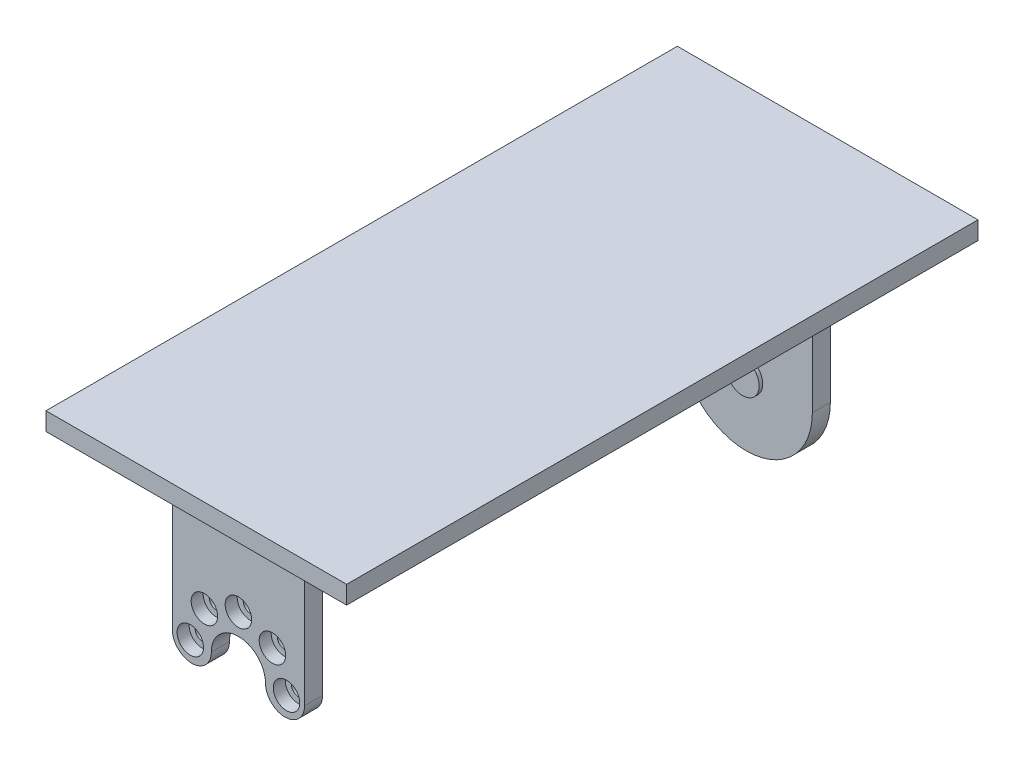
SolidWorks part; units mm, degrees
ref_plane "Plano frontal" through (0, 0, 0) normal (0, 0, 1) x (1, 0, 0)
ref_plane "Plano superior" through (0, 0, 0) normal (0, 1, 0) x (1, 0, 0)
ref_plane "Plano direito" through (0, 0, 0) normal (1, 0, 0) x (0, 0, -1)
sketch "Esboço1" plane through (0, 0, 0) normal (0, 0, 1) x (1, 0, 0)
  line L0 (11, 0) -> (11, 25)
  line L1 (11, 25) -> (-11, 25)
  line L2 (-11, 25) -> (-11, 0)
  arc A3 (11, 0) -> (4.5, 0) centre (7.75, 0) cw
  arc A8 (4.5, 0) -> (-4.5, 0) centre (0, 0) ccw
  arc A10 (-4.5, 0) -> (-11, 0) centre (-7.75, 0) cw
  dimension "D1" = 25
extrude "Ressalto-extrusão1" add sketch "Esboço1" along normal blind 3
sketch "Esboço2" plane through (0, 25, 0) normal (0, 1, 0) x (1, 0, 0)
  line L1 (-25, -10) -> (25, -10)
  line L2 (-25, -10) -> (-25, 95)
  line L3 (-25, 95) -> (25, 95)
  line L4 (25, -10) -> (25, 95)
  line L5 (11, -3) -> (-11, -3) construction
  point P7 (0, -3)
  point P8 (0, -10)
  dimension "D1" = 105
  dimension "D2" = 50
  dimension "D3" = 7
extrude "Ressalto-extrusão2" add sketch "Esboço2" along normal blind 3
ref_plane "Plano1" through (0, 0, -81.45) normal (0, 0, -1) x (-1, 0, 0)
sketch "Esboço3" plane through (0, 0, -81.45) normal (0, 0, -1) x (-1, 0, 0)
  line L1 (-11, 0) -> (-11, 25)
  line L2 (-11, 25) -> (11, 25)
  line L3 (11, 25) -> (11, 0)
  arc A0 (-11, 0) -> (11, 0) centre (0, 0) ccw
  dimension "D1" = 22
extrude "Ressalto-extrusão3" add sketch "Esboço3" along normal blind 3
hole_wizard "Rebaixo para SHCS M21" positions "Esboço4" profile "Esboço5" counterbore size "M2" standard "Ansi Metric" end condition up to next
sketch "Esboço4" plane through (0, 0, 3) normal (0, 0, 1) x (1, 0, 0)
  arc A0 (8.8, 0) -> (7.2, 0) centre (8, 0) ccw construction
  point P0 (8, 0)
sketch "Esboço5" plane through (8, 0, 3) normal (1, 0, 0) x (0, -1, 0)
  line L0 (0, 0) -> (0, 3)
  line L1 (0, 3) -> (1.2, 3)
  line L3 (1.2, 3) -> (1.2, 2)
  line L4 (1.2, 2) -> (2.2, 2)
  line L5 (2.2, 2) -> (2.2, 0)
  line L7 (2.2, 0) -> (0, 0)
  line L11 (0, -6.35) -> (0, 107.95) construction
  dimension "Thru Hole Dia." = 2.4
  dimension "Thru Hole Depth" = 3
  dimension "C'Bore Dia." = 4.4
  dimension "C'Bore Depth" = 2
pattern_circular "PadrãoCircular1" count 5 over 180 about axis through (0, 0, 3) along (0, 0, -1) of "Rebaixo para SHCS M21" reverse direction yes
sketch "Esboço6" plane through (0, 0, 0) normal (1, 0, 0) x (0, 0, -1)
  line L0 (-10, 25) -> (-3, 25) construction
  line L3 (-3, 25) -> (-3, 18) construction
  line L4 (-3, 0) -> (-3, 25) construction
  line L5 (-3, 18) -> (-10, 25)
rib "Nervura1" sketch "Esboço6" sketch "Esboço6" thickness 15 extrusion direction parallel to sketch draft on no parameters "D1"=15
sketch "Esboço7" plane through (0, 0, 3) normal (0, 0, 1) x (1, 0, 0)
  line L0 (-7.5, 25) -> (7.5, 25) construction
  line L1 (-5, 25) -> (5, 25)
  line L2 (-5, 25) -> (-5, 18)
  line L3 (-5, 18) -> (5, 18)
  line L4 (5, 25) -> (5, 18)
  line L5 (7.5, 18) -> (-7.5, 18) construction
  point P8 (0, 18)
  point P9 (0, 18)
  dimension "D1" = 10
extrude "Corte-extrusão1" cut sketch "Esboço7" along normal up to surface (7 mm away) up to face at (0, 21.5, 6.5)
sketch "Esboço8" plane through (0, 0, 0) normal (1, 0, 0) x (0, 0, -1)
  line L0 (0, 18) -> (7, 25)
  line L1 (0, 0) -> (0, 25) construction
  line L2 (-10, 25) -> (95, 25) construction
  line L5 (-10, 25) -> (-3, 18) construction
rib "Nervura7" sketch "Esboço8" sketch "Esboço8" thickness 15 extrusion direction parallel to sketch draft on no parameters "D1"=15
sketch "Esboço9" plane through (0, 0, 0) normal (0, 0, -1) x (-1, 0, 0)
  line L0 (-7.5, 18) -> (7.5, 18) construction
  line L1 (-5, 18) -> (5, 18)
  line L2 (-5, 18) -> (-5, 25)
  line L3 (-5, 25) -> (5, 25)
  line L4 (5, 18) -> (5, 25)
  line L5 (-11, 25) -> (-7.5, 25) construction
  point P8 (0, 18)
  point P9 (0, 18)
  dimension "D1" = 10
extrude "Corte-extrusão2" cut sketch "Esboço9" along normal up to surface up to face at (0, 21.5, -3.5)
pattern_linear "Padrão linear1" count 2 spacing 84.45 along (0, 0, -1) of "Nervura1", "Nervura7", "Corte-extrusão2", "Corte-extrusão1"
sketch "Esboço10" plane through (0, 0, -81.45) normal (0, 0, 1) x (1, 0, 0)
  circle A0 centre (0, 0) radius 2.75
  circle A2 centre (0, 0) radius 3.25 construction
  dimension "D1" = 0.5
extrude "Ressalto-extrusão4" add sketch "Esboço10" along normal offset from surface (0.6 mm away) 0.25 contours A0
